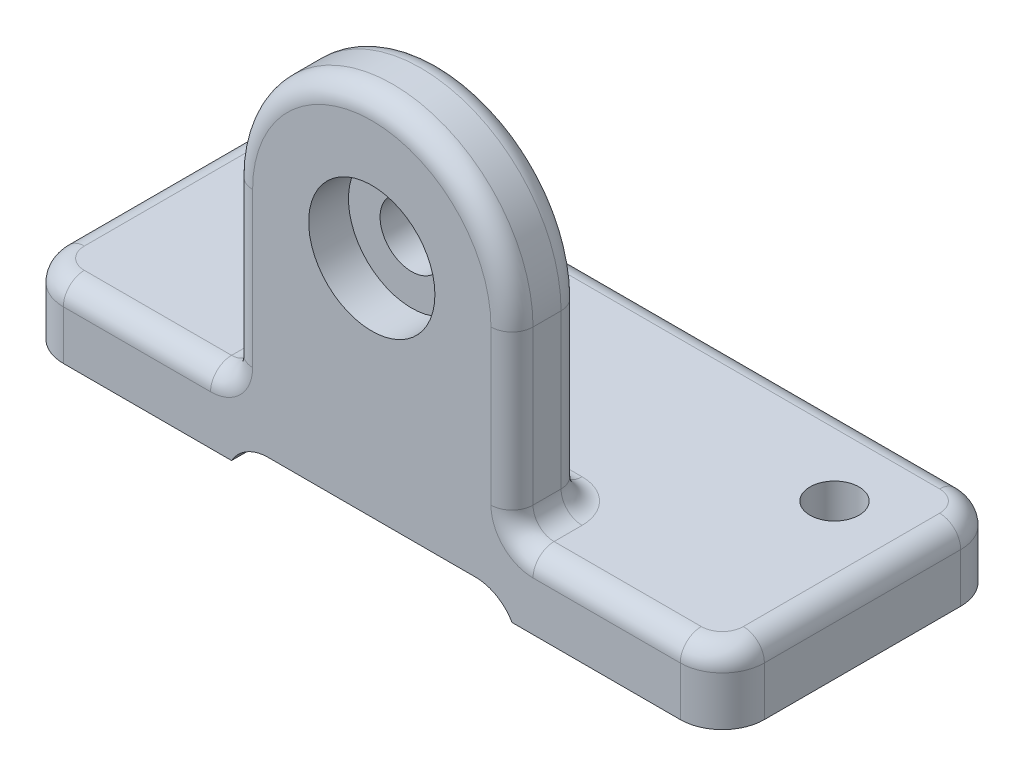
SolidWorks part; units mm, degrees
ref_plane "Front Plane" through (0, 0, 0) normal (0, 0, 1) x (1, 0, 0)
ref_plane "Top Plane" through (0, 0, 0) normal (0, 1, 0) x (1, 0, 0)
ref_plane "Right Plane" through (0, 0, 0) normal (1, 0, 0) x (0, 0, -1)
sketch "Sketch1" plane through (0, 0, 0) normal (0, 1, 0) x (1, 0, 0)
  line L1 (0, 0) -> (100, 0)
  line L2 (0, 0) -> (0, 40)
  line L3 (0, 40) -> (100, 40)
  line L4 (100, 0) -> (100, 40)
  dimension "D1" = 100
  dimension "D2" = 40
extrude "Base Plate" add sketch "Sketch1" along normal blind 10
sketch "Sketch2" plane through (0, 0, 0) normal (0, 0, 1) x (1, 0, 0)
  line L0 (30, 0) -> (30, 35)
  line L1 (0, 0) -> (100, 0) construction
  line L2 (70, 35) -> (70, 0)
  line L3 (70, 0) -> (30, 0)
  line L4 (0, 10) -> (0, 0) construction
  arc A0 (30, 35) -> (70, 35) centre (50, 35) cw
  dimension "D1" = 20
  dimension "D2" = 50
  dimension "D3" = 35
extrude "Vert Boss" add sketch "Sketch2" against normal blind 10
sketch "Sketch5" plane through (0, 0, 0) normal (0, 0, 1) x (1, 0, 0)
  line L0 (0, 0) -> (100, 0) construction
  line L1 (30, 0) -> (70, 0)
  line L2 (30, 0) -> (30, 3)
  line L3 (30, 3) -> (70, 3)
  line L4 (70, 0) -> (70, 3)
  line L5 (30, 35) -> (30, 10) construction
  line L6 (70, 10) -> (70, 35) construction
  dimension "D1" = 3
extrude "Slot" cut sketch "Sketch5" against normal through all
hole_wizard "Ø7.0 (7) 直徑孔1" positions "Sketch9" profile "Sketch8" hole size "Ø7.0" standard "Ansi Metric" end condition through all
sketch "Sketch9" plane through (0, 10, 0) normal (0, 1, 0) x (-1, 0, 0)
  line L0 (-100, 0) -> (-100, -40) construction
  line L1 (-100, -40) -> (0, -40) construction
  line L2 (0, -40) -> (0, 0) construction
  point P0 (-88, -28)
  point P1 (-12, -28)
  dimension "D1" = 12
  dimension "D2" = 12
  dimension "D3" = 12
sketch "Sketch8" plane through (88, 10, -28) normal (1, 0, 0) x (0, 0, 1)
  line L0 (0, 0) -> (0, 10)
  line L1 (0, 10) -> (3.5, 10)
  line L2 (3.5, 10) -> (3.5, 0)
  line L5 (3.5, 0) -> (0, 0)
  line L11 (0, -6.35) -> (0, 107.95) construction
  dimension "Thru Hole Dia." = 7
  dimension "Thru Hole Depth" = 10
hole_wizard "CBORE for M8 Hex Head Bolt1" positions "Sketch4" profile "Sketch3" counterbore size "M8" standard "Ansi Metric" end condition through all
sketch "Sketch4" plane through (0, 0, 0) normal (0, 0, 1) x (1, 0, 0)
  point P0 (50, 35)
sketch "Sketch3" plane through (50, 35, 0) normal (1, 0, 0) x (0, -1, 0)
  line L0 (0, 0) -> (0, 40)
  line L1 (0, 40) -> (4.5, 40)
  line L3 (4.5, 40) -> (4.5, 5.68)
  line L4 (4.5, 5.68) -> (9.005, 5.68)
  line L5 (9.005, 5.68) -> (9.005, 0)
  line L7 (9.005, 0) -> (0, 0)
  line L11 (0, -6.35) -> (0, 107.95) construction
  dimension "Thru Hole Dia." = 9
  dimension "Thru Hole Depth" = 40
  dimension "C'Bore Dia." = 18.01
  dimension "C'Bore Depth" = 5.68
fillet "圓角1" radius 6 6 edges at (70, 3, -20) (30, 3, -20) (0, 5, 0) (0, 5, -40) (100, 5, -40) (100, 5, 0)
fillet "圓角2" radius 3 18 edges at (1.7574, 10, -38.2426) (0, 10, -20) (50, 10, -40) (1.7574, 10, -1.7574) (98.2426, 10, -38.2426) (18, 10, 0) (100, 10, -20) (30, 10, -5) (98.2426, 10, -1.7574) (50, 10, -10) (82, 10, 0) (70, 22.5, -10) (30, 22.5, -10) (70, 22.5, 0) (30, 22.5, 0) (70, 10, -5) (50, 55, -10) (50, 55, 0)
